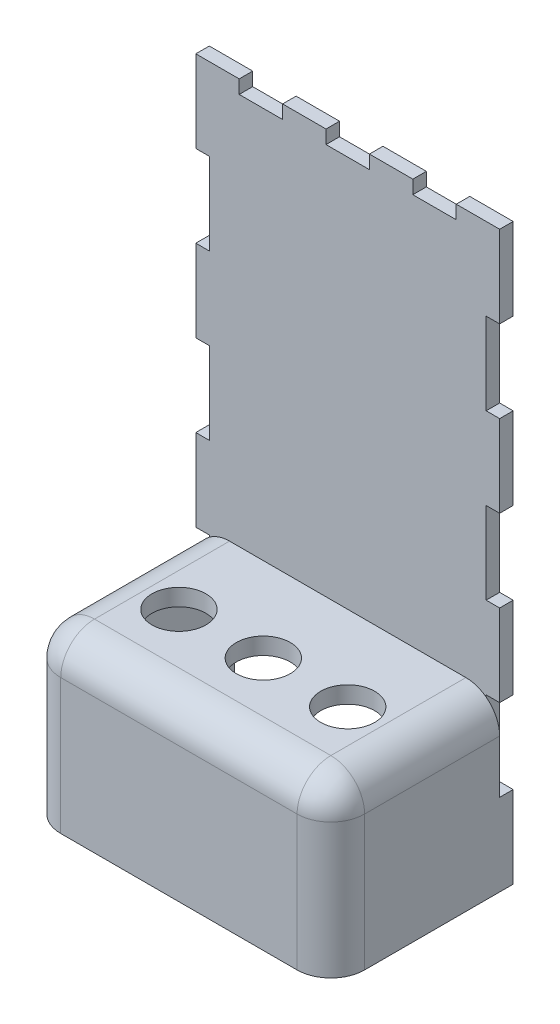
SolidWorks part; units mm, degrees
ref_plane "Front Plane" through (0, 0, 0) normal (0, 0, 1) x (1, 0, 0)
ref_plane "Top Plane" through (0, 0, 0) normal (0, 1, 0) x (1, 0, 0)
ref_plane "Right Plane" through (0, 0, 0) normal (1, 0, 0) x (0, 0, -1)
sketch "Buitenafmeting Rechthoek" plane through (0, 0, 0) normal (0, 0, 1) x (1, 0, 0)
  line L1 (0, 0) -> (90, 0)
  line L2 (0, 0) -> (0, 170)
  line L3 (0, 170) -> (90, 170)
  line L4 (90, 0) -> (90, 170)
  dimension "D1" = 90
  dimension "D2" = 170
extrude "Plaat" add sketch "Buitenafmeting Rechthoek" against normal blind 4
sketch "Tand Hor" plane through (0, 0, 0) normal (0, 0, 1) x (1, 0, 0)
  line L1 (90, 170) -> (0, 170) construction
  line L2 (12.8571, 170) -> (25.7143, 170)
  line L3 (12.8571, 170) -> (12.8571, 166)
  line L4 (12.8571, 166) -> (25.7143, 166)
  line L6 (25.7143, 170) -> (25.7143, 166)
  dimension "D1" = 4
  dimension "D2" = 12.8571
  dimension "D3" = 12.8571
extrude "Tand Boven" cut sketch "Tand Hor" against normal through all
pattern_linear "Tanden Patroon Boven" count 3 spacing 25.7143 along (1, 0, 0) of "Tand Boven"
sketch "Tand Ver" plane through (0, 0, 0) normal (0, 0, 1) x (1, 0, 0)
  line L0 (0, 170) -> (0, 0) construction
  line L1 (0, 145.7143) -> (4, 145.7143)
  line L2 (0, 145.7143) -> (0, 121.4286)
  line L3 (0, 121.4286) -> (4, 121.4286)
  line L4 (4, 145.7143) -> (4, 121.4286)
  dimension "D1" = 4
  dimension "D2" = 24.2857
  dimension "D3" = 145.7143
extrude "Tand Links" cut sketch "Tand Ver" against normal through all
pattern_linear "Tanden Patroon Links" count 3 spacing 48.5714 along (0, -1, 0) of "Tand Links"
sketch "Tand O" plane through (0, 0, 0) normal (0, 0, 1) x (1, 0, 0)
  line L0 (0, 0) -> (90, 0) construction
  line L1 (12.8571, 0) -> (25.7143, 0)
  line L2 (12.8571, 0) -> (12.8571, 4)
  line L3 (12.8571, 4) -> (25.7143, 4)
  line L4 (25.7143, 0) -> (25.7143, 4)
  dimension "D1" = 4
  dimension "D2" = 12.8571
  dimension "D3" = 12.8571
extrude "Tand Onder" cut sketch "Tand O" against normal through all
pattern_linear "Tanden Patroon Onder" count 3 spacing 25.7143 along (1, 0, 0) of "Tand Onder"
sketch "Tand R" plane through (0, 0, 0) normal (0, 0, 1) x (1, 0, 0)
  line L0 (90, 0) -> (90, 170) construction
  line L1 (90, 145.7143) -> (86, 145.7143)
  line L2 (90, 145.7143) -> (90, 121.4286)
  line L3 (90, 121.4286) -> (86, 121.4286)
  line L4 (86, 145.7143) -> (86, 121.4286)
  dimension "D1" = 4
  dimension "D2" = 24.2857
  dimension "D3" = 145.7143
extrude "Tand Rechts" cut sketch "Tand R" against normal through all
pattern_linear "Tanden Patroon Rechts" count 3 spacing 48.5714 along (0, -1, 0) of "Tand Rechts"
sketch "Sketch1" plane through (0, 0, 0) normal (0, 0, 1) x (1, 0, 0)
  line L0 (90, 48.5714) -> (90, 72.8571) construction
  line L1 (0, 0) -> (90, 0)
  line L2 (0, 0) -> (0, 50)
  line L3 (0, 50) -> (90, 50)
  line L4 (90, 0) -> (90, 50)
  dimension "D1" = 50
extrude "Boss-Extrude1" add sketch "Sketch1" along normal blind 50
sketch "Sketch2" plane through (0, 0, -4) normal (0, 0, -1) x (-1, 0, 0)
  line L0 (0, 24.2857) -> (0, 0) construction
  line L1 (-82.5, 45) -> (-7.5, 45)
  line L2 (-82.5, 45) -> (-82.5, 5)
  line L3 (-82.5, 5) -> (-7.5, 5)
  line L4 (-7.5, 45) -> (-7.5, 5)
  line L5 (-25.7143, 0) -> (-38.5714, 0) construction
  dimension "D1" = 75
  dimension "D2" = 40
  dimension "D3" = 7.5
  dimension "D4" = 5
extrude "Cut-Extrude1" cut sketch "Sketch2" against normal blind 50
sketch "Sketch3" plane through (0, 50, 0) normal (0, 1, 0) x (1, 0, 0)
  line L0 (90, -50) -> (0, -50) construction
  line L1 (90, -50) -> (90, 0) construction
  line L2 (0, -50) -> (0, 0) construction
  circle A0 centre (45, -25) radius 8
  circle A1 centre (70, -25) radius 8
  circle A2 centre (20, -25) radius 8
  dimension "D1" = 16
  dimension "D5" = 16
  dimension "D6" = 16
  dimension "D2" = 25
  dimension "D3" = 45
  dimension "D4" = 20
  dimension "D7" = 20
extrude "Cut-Extrude3" cut sketch "Sketch3" against normal blind 24
fillet "Fillet1" radius 10 5 edges at (0, 50, 25) (0, 25, 50) (90, 25, 50) (90, 50, 25) (45, 50, 50)
equation "\"D1@Buitenafmeting Rechthoek\"= \"Lengte\""
equation "\"D2@Buitenafmeting Rechthoek\" = \"Hoogte\""
equation "\"D1@Plaat\" = \"Dikte\""
equation "\"D3@Tanden Patroon Boven\" = \"LengteHorTand\" * 2"
equation "\"D1@Tanden Patroon Boven\" = \"nPatroonHor\""
equation "\"LengteHorTand\"= \"Lengte\" / \"nHor\"'Spatie tussen verschillende tanden in de lengte"
equation "\"nPatroonHor\"= ( \"nHor\" + 1 ) / 2 - \"GrensHor\"'Aantal kopies van tanden in de lengte"
equation "\"D1@Tand Hor\" = \"Dikte\""
equation "\"D2@Tand Hor\" = \"LengteHorTand\""
equation "\"D1@Tand Ver\" = \"Dikte\""
equation "\"LengteVertTand\"= \"Hoogte\" / \"nVert\"'Spatie tussen verschillende tanden in de hoogte"
equation "\"nPatroonVert\"= ( \"nVert\" + 1 ) / 2 - \"GrensVert\"'Aantal kopies van tanden in de hoogte"
equation "\"D2@Tand Ver\"=\"LengteVertTand\""
equation "\"D3@Tanden Patroon Links\"=\"LengteVertTand\"*2"
equation "\"D3@Tanden Patroon Rechts\"=\"LengteVertTand\"*2"
equation "\"D1@Tanden Patroon Rechts\"=\"nPatroonVert\""
equation "\"D3@Tanden Patroon Onder\"=\"LengteHorTand\"*2"
equation "\"D1@Tanden Patroon Onder\"=\"nPatroonHor\""
equation "\"D1@Tanden Patroon Links\"=\"nPatroonVert\""
equation "\"D3@Tand Ver\"=\"Hoogte\"-\"GrensVert\"*\"LengteVertTand\""
equation "\"D2@Tand R\" = \"LengteVertTand\""
equation "\"D3@Tand R\" = \"Hoogte\" - \"GrensVert\" * \"LengteVertTand\""
equation "\"D2@Tand O\"=\"LengteHorTand\""
equation "\"D3@Tand Hor\"=\"GrensHor\"*\"LengteHorTand\""
equation "\"D3@Tand O\"=\"GrensHor\"*\"LengteHorTand\""
equation "\"Tand Boven\"= IIF ( \"plaatsTandenBoven\" , \"unsuppressed\" , \"suppressed\" )"
equation "\"Tanden Patroon Boven\"= IIF ( \"plaatsTandenBoven\" , \"unsuppressed\" , \"suppressed\" )"
equation "\"Tand Links\"= IIF ( \"plaatsTandenLinks\" , \"unsuppressed\" , \"suppressed\" )"
equation "\"Tanden Patroon Links\"= IIF ( \"plaatsTandenLinks\" , \"unsuppressed\" , \"suppressed\" )"
equation "\"Tand Onder\"= IIF ( \"plaatsTandenOnder\" , \"unsuppressed\" , \"suppressed\" )"
equation "\"Tanden Patroon Onder\"= IIF ( \"plaatsTandenOnder\" , \"unsuppressed\" , \"suppressed\" )"
equation "\"Tand Rechts\"= IIF ( \"plaatsTandenRechts\" , \"unsuppressed\" , \"suppressed\" )"
equation "\"Tanden Patroon Rechts\"= IIF ( \"plaatsTandenRechts\" , \"unsuppressed\" , \"suppressed\" )"
equation "\"D1@Tand O\"=\"Dikte\""
equation "\"D1@Tand R\"=\"Dikte\""
